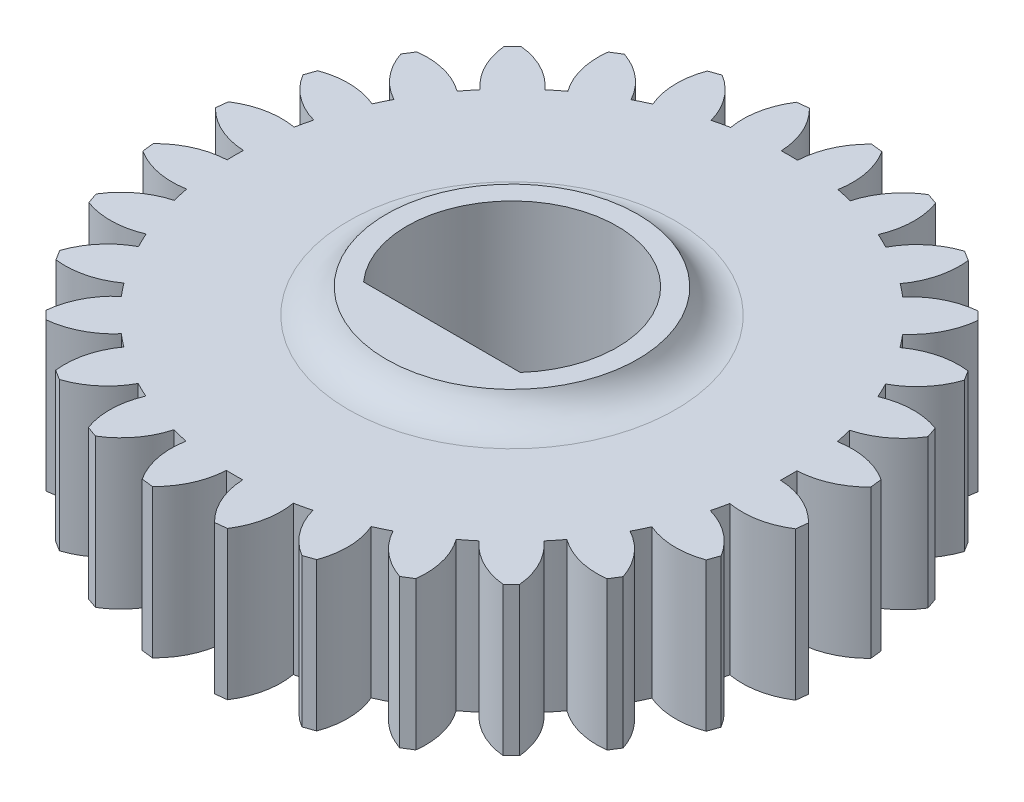
SolidWorks part; units mm, degrees
ref_plane "Front Plane" through (0, 0, 0) normal (0, 0, 1) x (1, 0, 0)
ref_plane "Top Plane" through (0, 0, 0) normal (0, 1, 0) x (1, 0, 0)
ref_plane "Right Plane" through (0, 0, 0) normal (1, 0, 0) x (0, 0, -1)
sketch "Sketch1" plane through (0, 0, 0) normal (0, 1, 0) x (1, 0, 0)
  line L0 (-7.1948, -3.6172) -> (7.6929, -1.7858) construction
  line L1 (63.2764, 117.5231) -> (418.9939, 154.8824) construction
  line L2 (-7.5765, -2.5699) -> (7.4735, -2.5699) construction
  line L3 (3.5579, -5.6781) -> (4.2438, -6.7727) construction
  line L4 (3.0873, -5.9731) -> (4.0286, -5.3832) construction
  line L5 (4.1237, -6.848) -> (4.3639, -6.6975)
  line L6 (2.4965, -7.5939) -> (2.7641, -7.5006)
  line L7 (0.7441, -7.959) -> (1.0258, -7.9276)
  line L8 (-1.0456, -7.925) -> (-0.764, -7.9571)
  line L9 (-2.7829, -7.4937) -> (-2.5154, -7.5876)
  line L10 (-4.3806, -6.6865) -> (-4.1408, -6.8376)
  line L11 (-5.7587, -5.5441) -> (-5.5585, -5.7448)
  line L12 (-6.848, -4.1237) -> (-6.6975, -4.3639)
  line L13 (-7.5939, -2.4965) -> (-7.5006, -2.7641)
  line L14 (-7.959, -0.7441) -> (-7.9276, -1.0258)
  line L15 (-7.925, 1.0456) -> (-7.9571, 0.764)
  line L16 (-7.4937, 2.7829) -> (-7.5876, 2.5154)
  line L17 (-6.6865, 4.3806) -> (-6.8376, 4.1408)
  line L18 (-5.5441, 5.7587) -> (-5.7448, 5.5585)
  line L19 (-4.1237, 6.848) -> (-4.3639, 6.6975)
  line L20 (-2.4965, 7.5939) -> (-2.7641, 7.5006)
  line L21 (-0.7441, 7.959) -> (-1.0258, 7.9276)
  line L22 (1.0456, 7.925) -> (0.764, 7.9571)
  line L23 (2.7829, 7.4937) -> (2.5154, 7.5876)
  line L24 (4.3806, 6.6865) -> (4.1408, 6.8376)
  line L25 (5.7587, 5.5441) -> (5.5585, 5.7448)
  line L26 (6.848, 4.1237) -> (6.6975, 4.3639)
  line L27 (7.5939, 2.4965) -> (7.5006, 2.7641)
  line L28 (7.959, 0.7441) -> (7.9276, 1.0258)
  line L29 (7.925, -1.0456) -> (7.9571, -0.764)
  line L30 (7.4937, -2.7829) -> (7.5876, -2.5154)
  line L31 (6.6865, -4.3806) -> (6.8376, -4.1408)
  line L32 (5.5441, -5.7587) -> (5.7448, -5.5585)
  circle A0 centre (0, 0) radius 2.55
  circle A1 centre (0, 0) radius 7.9925 construction
  circle A2 centre (0, 0) radius 6.7008 construction
  arc A3 (3.0873, -5.9731) -> (4.1237, -6.848) centre (4.7091, -5.1032) ccw
  arc A4 (4.0286, -5.3832) -> (4.3639, -6.6975) centre (2.5384, -6.4633) cw
  arc A5 (3.0873, -5.9731) -> (4.0286, -5.3832) centre (0, 0) ccw
  circle A6 centre (0, 0) radius 6.7237
  arc A7 (2.7297, -6.1447) -> (2.7641, -7.5006) centre (1.0366, -6.8661) cw
  arc A8 (1.6807, -6.5103) -> (2.4965, -7.5939) centre (3.4555, -6.0231) ccw
  arc A9 (1.2939, -6.5981) -> (1.0258, -7.9276) centre (-0.5173, -6.9246) cw
  arc A10 (0.1899, -6.7211) -> (0.7441, -7.959) centre (2.0286, -6.641) ccw
  arc A11 (-0.2067, -6.7206) -> (-0.764, -7.9571) centre (-2.0452, -6.6359) cw
  arc A12 (-1.3104, -6.5948) -> (-1.0456, -7.925) centre (0.5, -6.9259) ccw
  arc A13 (-1.697, -6.5061) -> (-2.5154, -7.5876) centre (-3.4705, -6.0144) cw
  arc A14 (-2.745, -6.1379) -> (-2.7829, -7.4937) centre (-1.0537, -6.8635) ccw
  arc A15 (-3.1022, -5.9653) -> (-4.1408, -6.8376) centre (-4.7218, -5.0914) cw
  arc A16 (-4.042, -5.3732) -> (-4.3806, -6.6865) centre (-2.5546, -6.4569) ccw
  arc A17 (-4.3518, -5.1255) -> (-5.5585, -5.7448) centre (-5.7364, -3.913) cw
  arc A18 (-5.1363, -4.339) -> (-5.7587, -5.5441) centre (-3.9273, -5.7266) ccw
  arc A19 (-5.3832, -4.0286) -> (-6.6975, -4.3639) centre (-6.4633, -2.5384) cw
  arc A20 (-5.9731, -3.0873) -> (-6.848, -4.1237) centre (-5.1032, -4.7091) ccw
  arc A21 (-6.1447, -2.7297) -> (-7.5006, -2.7641) centre (-6.8661, -1.0366) cw
  arc A22 (-6.5103, -1.6807) -> (-7.5939, -2.4965) centre (-6.0231, -3.4555) ccw
  arc A23 (-6.5981, -1.2939) -> (-7.9276, -1.0258) centre (-6.9246, 0.5173) cw
  arc A24 (-6.7211, -0.1899) -> (-7.959, -0.7441) centre (-6.641, -2.0286) ccw
  arc A25 (-6.7206, 0.2067) -> (-7.9571, 0.764) centre (-6.6359, 2.0452) cw
  arc A26 (-6.5948, 1.3104) -> (-7.925, 1.0456) centre (-6.9259, -0.5) ccw
  arc A27 (-6.5061, 1.697) -> (-7.5876, 2.5154) centre (-6.0144, 3.4705) cw
  arc A28 (-6.1379, 2.745) -> (-7.4937, 2.7829) centre (-6.8635, 1.0537) ccw
  arc A29 (-5.9653, 3.1022) -> (-6.8376, 4.1408) centre (-5.0914, 4.7218) cw
  arc A30 (-5.3732, 4.042) -> (-6.6865, 4.3806) centre (-6.4569, 2.5546) ccw
  arc A31 (-5.1255, 4.3518) -> (-5.7448, 5.5585) centre (-3.913, 5.7364) cw
  arc A32 (-4.339, 5.1363) -> (-5.5441, 5.7587) centre (-5.7266, 3.9273) ccw
  arc A33 (-4.0286, 5.3832) -> (-4.3639, 6.6975) centre (-2.5384, 6.4633) cw
  arc A34 (-3.0873, 5.9731) -> (-4.1237, 6.848) centre (-4.7091, 5.1032) ccw
  arc A35 (-2.7297, 6.1447) -> (-2.7641, 7.5006) centre (-1.0366, 6.8661) cw
  arc A36 (-1.6807, 6.5103) -> (-2.4965, 7.5939) centre (-3.4555, 6.0231) ccw
  arc A37 (-1.2939, 6.5981) -> (-1.0258, 7.9276) centre (0.5173, 6.9246) cw
  arc A38 (-0.1899, 6.7211) -> (-0.7441, 7.959) centre (-2.0286, 6.641) ccw
  arc A39 (0.2067, 6.7206) -> (0.764, 7.9571) centre (2.0452, 6.6359) cw
  arc A40 (1.3104, 6.5948) -> (1.0456, 7.925) centre (-0.5, 6.9259) ccw
  arc A41 (1.697, 6.5061) -> (2.5154, 7.5876) centre (3.4705, 6.0144) cw
  arc A42 (2.745, 6.1379) -> (2.7829, 7.4937) centre (1.0537, 6.8635) ccw
  arc A43 (3.1022, 5.9653) -> (4.1408, 6.8376) centre (4.7218, 5.0914) cw
  arc A44 (4.042, 5.3732) -> (4.3806, 6.6865) centre (2.5546, 6.4569) ccw
  arc A45 (4.3518, 5.1255) -> (5.5585, 5.7448) centre (5.7364, 3.913) cw
  arc A46 (5.1363, 4.339) -> (5.7587, 5.5441) centre (3.9273, 5.7266) ccw
  arc A47 (5.3832, 4.0286) -> (6.6975, 4.3639) centre (6.4633, 2.5384) cw
  arc A48 (5.9731, 3.0873) -> (6.848, 4.1237) centre (5.1032, 4.7091) ccw
  arc A49 (6.1447, 2.7297) -> (7.5006, 2.7641) centre (6.8661, 1.0366) cw
  arc A50 (6.5103, 1.6807) -> (7.5939, 2.4965) centre (6.0231, 3.4555) ccw
  arc A51 (6.5981, 1.2939) -> (7.9276, 1.0258) centre (6.9246, -0.5173) cw
  arc A52 (6.7211, 0.1899) -> (7.959, 0.7441) centre (6.641, 2.0286) ccw
  arc A53 (6.7206, -0.2067) -> (7.9571, -0.764) centre (6.6359, -2.0452) cw
  arc A54 (6.5948, -1.3104) -> (7.925, -1.0456) centre (6.9259, 0.5) ccw
  arc A55 (6.5061, -1.697) -> (7.5876, -2.5154) centre (6.0144, -3.4705) cw
  arc A56 (6.1379, -2.745) -> (7.4937, -2.7829) centre (6.8635, -1.0537) ccw
  arc A57 (5.9653, -3.1022) -> (6.8376, -4.1408) centre (5.0914, -4.7218) cw
  arc A58 (5.3732, -4.042) -> (6.6865, -4.3806) centre (6.4569, -2.5546) ccw
  arc A59 (5.1255, -4.3518) -> (5.7448, -5.5585) centre (3.913, -5.7364) cw
  arc A60 (4.339, -5.1363) -> (5.5441, -5.7587) centre (5.7266, -3.9273) ccw
  point P16 (3.5579, -5.6781)
  point P18 (4.2438, -6.7727)
  point P188 (0, 0)
  dimension "D1" = 5.1
  dimension "D4" = 15.9849
  dimension "D5" = 13.4015
  dimension "D6" = 0.2835
  dimension "D8" = 28
  dimension "D2" = 15
  dimension "D3" = 15.05
  dimension "D7" = 1.1108
extrude "Boss-Extrude2" add sketch "Sketch1" along normal blind 3.6 contours A6 A32 L18 A31 | A6 A34 L19 A33 | A6 A36 L20 A35 | A6 A30 L17 A29 | A6 A38 L21 A37 | A6 A40 L22 A39 | A6 A42 L23 A41 | A6 A44 L24 A43 | A6 A46 L25 A45 | A6 A48 L26 A47 | A6 A28 L16 A27 | A6 A26 L15 A25 | A6 A24 L14 A23 | A6 A22 L13 A21 | A6 A20 L12 A19 | A6 A18 L11 A17 | A6 A16 L10 A15 | A6 A14 L9 A13 | A6 A12 L8 A11 | A6 A10 L7 A9 | A6 A8 L6 A7 | A5 A3 L5 A4 | A6 A60 L32 A59 | A6 A58 L31 A57 | A6 A56 L30 A55 | A6 A54 L29 A53 | A6 A52 L28 A51 | A6 A50 L27 A49 | A5 A6 region at (3.8532, 0, 6.1494) region at (2.8275, 0, 5.8901) region at (2.3882, 0, 6.8526) region at (5.125, 0, 5.1378) region at (0.8035, 0, 7.2122) region at (6.1397, 0, 3.8686) region at (-0.8215, 0, 7.2102) region at (6.8466, 0, 2.4053) region at (-2.4053, 0, 6.8466) region at (7.2102, 0, 0.8215) region at (-3.8686, 0, 6.1397) region at (7.2122, 0, -0.8035) region at (-5.1378, 0, 5.125) region at (6.8526, 0, -2.3882) region at (-6.1494, 0, 3.8532) region at (6.1494, 0, -3.8532) region at (-6.8526, 0, 2.3882) region at (5.1378, 0, -5.125) region at (-7.2122, 0, 0.8035) region at (3.8686, 0, -6.1397) region at (-7.2102, 0, -0.8215) region at (2.4053, 0, -6.8466) region at (-6.8466, 0, -2.4053) region at (0.8215, 0, -7.2102) region at (-6.1397, 0, -3.8686) region at (-0.8035, 0, -7.2122) region at (-5.125, 0, -5.1378) region at (-2.3882, 0, -6.8526) region at (-3.8532, 0, -6.1494)
sketch "Sketch2" plane through (0, 3.6, 0) normal (0, 1, 0) x (1, 0, 0)
  line L0 (0, 2.55) -> (0, -1.7) construction
  line L1 (-1.9007, -1.7) -> (1.9007, -1.7)
  circle A0 centre (0, 0) radius 2.55 construction
  arc A1 (-1.9007, -1.7) -> (1.9007, -1.7) centre (0, 0) ccw
  point P9 (0, -1.7)
  dimension "D1" = 4.25
extrude "Boss-Extrude3" add sketch "Sketch2" against normal blind 3.6
sketch "Sketch5" plane through (0, 3.6, 0) normal (0, 1, 0) x (1, 0, 0)
  line L0 (-1.9007, -1.7) -> (1.9007, -1.7)
  circle A0 centre (0, 0) radius 2.55
  circle A1 centre (0, 0) radius 3.05
extrude "Boss-Extrude6" add sketch "Sketch5" along normal blind 0.6 contours L0 A0 | A1 A0 region at (0, 3.6, 2.0454) region at (-2.9637, 3.6, 0)
fillet "Fillet3" radius 1 1 edges at (0, 3.6, 3.05)
